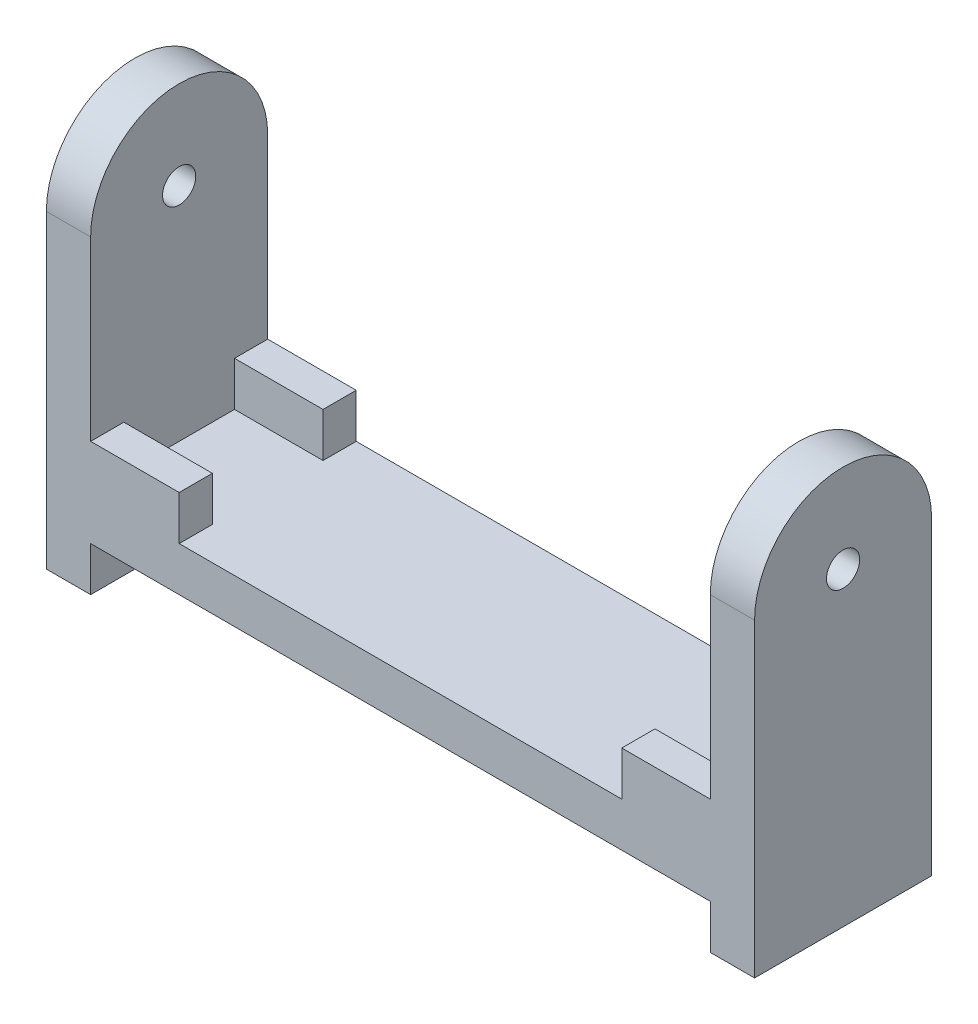
SolidWorks part; units mm, degrees
ref_plane "前基準面" through (0, 0, 0) normal (0, 0, 1) x (1, 0, 0)
ref_plane "上基準面" through (0, 0, 0) normal (0, 1, 0) x (1, 0, 0)
ref_plane "右基準面" through (0, 0, 0) normal (1, 0, 0) x (0, 0, -1)
sketch "草圖2" plane through (0, 0, 0) normal (1, 0, 0) x (0, 0, -1)
  line L0 (-40, 0) -> (-40, -120)
  line L1 (-40, -120) -> (40, -120)
  line L2 (40, -120) -> (40, 0)
  line L3 (0, 122.7537) -> (0, -552.4626) construction
  circle A0 centre (0, 0) radius 7.5
  arc A1 (40, 0) -> (-40, 0) centre (0, 0) ccw
  dimension "D1" = 15
  dimension "D3" = 40
  dimension "D2" = 120
extrude "填料-伸長1" add sketch "草圖2" along normal blind 320
sketch "草圖3" plane through (0, 0, -40) normal (0, 0, -1) x (-1, 0, 0)
  line L0 (-300, 40) -> (-300, -100)
  line L1 (0, 40) -> (-320, 40) construction
  line L2 (-300, -100) -> (-20, -100)
  line L3 (-20, -100) -> (-20, 40)
  line L4 (-20, 40) -> (-300, 40)
  line L5 (-320, -120) -> (0, -120) construction
  line L6 (-320, -120) -> (-320, 0) construction
  line L7 (0, -120) -> (0, 0) construction
  dimension "D1" = 20
  dimension "D2" = 20
  dimension "D3" = 20
extrude "除料-伸長1" cut sketch "草圖3" against normal through all
sketch "草圖4" plane through (0, -120, 0) normal (0, -1, 0) x (1, 0, 0)
  line L0 (-11.0995, 0) -> (327.2431, 0) construction
  line L1 (160, 40) -> (160, -40) construction
  line L2 (320, 40) -> (0, 40) construction
  line L3 (320, -40) -> (0, -40) construction
  line L5 (0, 40) -> (20, 40)
  line L6 (0, 40) -> (0, -40)
  line L7 (0, -40) -> (20, -40)
  line L8 (20, 40) -> (20, -40)
  line L9 (320, -40) -> (300, -40)
  line L10 (320, -40) -> (320, 40)
  line L11 (320, 40) -> (300, 40)
  line L12 (300, -40) -> (300, 40)
  dimension "D1" = 20
  dimension "D2" = 20
extrude "填料-伸長2" add sketch "草圖4" along normal blind 20
sketch "草圖5" plane through (0, -140, 0) normal (0, -1, 0) x (1, 0, 0)
  line L0 (-15.8081, 0) -> (313.4538, 0) construction
  line L1 (10, 40) -> (10, -40) construction
  line L2 (20, 40) -> (0, 40) construction
  line L3 (0, -40) -> (20, -40) construction
  line L4 (310, -40) -> (310, 40) construction
  line L5 (300, -40) -> (320, -40) construction
  line L6 (320, 40) -> (300, 40) construction
  circle A0 centre (10, 0) radius 5
  circle A1 centre (310, 0) radius 5
  dimension "D1" = 10
extrude "螺絲預留孔" cut sketch "草圖5" against normal blind 20
sketch "草圖7" plane through (0, -100, 0) normal (0, 1, 0) x (1, 0, 0)
  line L0 (-20.5166, 0) -> (321.5256, 0) construction
  line L1 (20, 40) -> (60, 40)
  line L2 (20, 40) -> (20, 25)
  line L3 (20, 25) -> (60, 25)
  line L4 (60, 40) -> (60, 25)
  line L5 (20, -40) -> (60, -40)
  line L6 (20, -40) -> (20, -25)
  line L7 (20, -25) -> (60, -25)
  line L8 (60, -40) -> (60, -25)
  line L9 (300, -40) -> (260, -40)
  line L10 (300, -40) -> (300, -25)
  line L11 (300, -25) -> (260, -25)
  line L12 (260, -40) -> (260, -25)
  line L13 (300, 40) -> (260, 40)
  line L14 (300, 40) -> (300, 25)
  line L15 (300, 25) -> (260, 25)
  line L16 (260, 40) -> (260, 25)
  line L17 (300, 40) -> (300, -40) construction
  dimension "D1" = 40
  dimension "D2" = 15
  dimension "D3" = 40
extrude "放馬達" add sketch "草圖7" along normal blind 20
